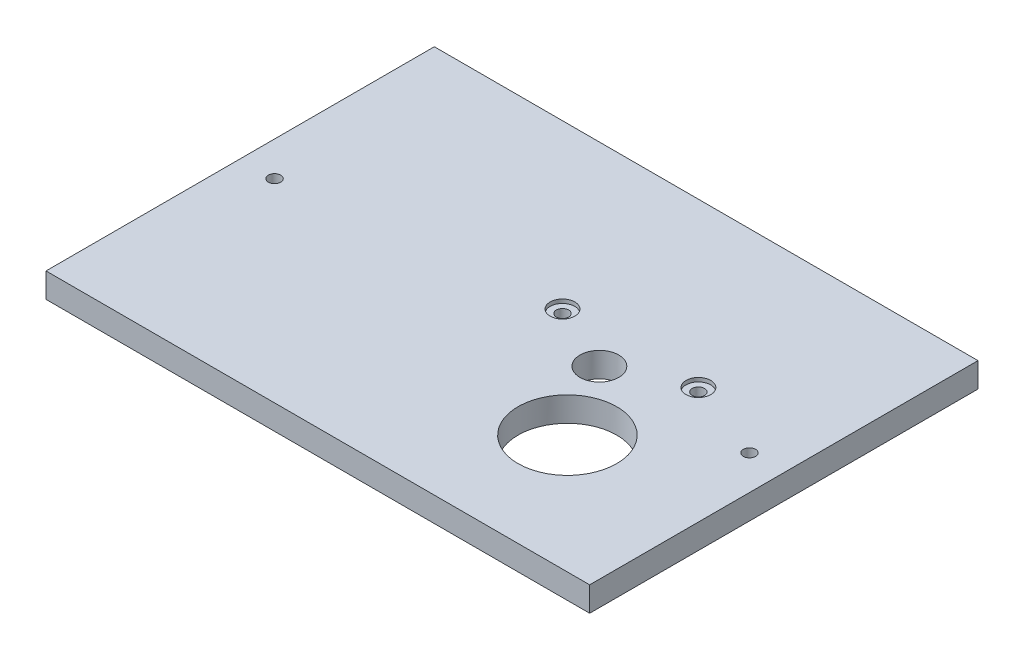
SolidWorks part; units mm, degrees
material "Oak"
ref_plane "Front Plane" through (0, 0, 0) normal (0, 0, 1) x (1, 0, 0)
ref_plane "Top Plane" through (0, 0, 0) normal (0, 1, 0) x (1, 0, 0)
ref_plane "Right Plane" through (0, 0, 0) normal (1, 0, 0) x (0, 0, -1)
sketch "Sketch1" plane through (0, 0, 0) normal (0, 1, 0) x (1, 0, 0)
  line L1 (0, 0) -> (140, 0)
  line L2 (0, 0) -> (0, 100)
  line L3 (0, 100) -> (140, 100)
  line L4 (140, 0) -> (140, 100)
  dimension "D1" = 140
  dimension "D2" = 100
extrude "Boss-Extrude1" add sketch "Sketch1" along normal blind 6.35
sketch "Sketch2" plane through (0, 6.35, 0) normal (0, 1, 0) x (1, 0, 0)
  line L0 (0, 50) -> (140, 50) construction
  line L1 (0, 100) -> (0, 0) construction
  line L2 (140, 0) -> (140, 100) construction
  line L3 (70, 100) -> (70, 0) construction
  line L4 (140, 100) -> (0, 100) construction
  line L5 (0, 0) -> (140, 0) construction
  line L6 (92.5, 50) -> (114.578, 11.7597) construction
  circle A0 centre (103.75, 30.5144) radius 12.705
  circle A1 centre (92.5, 50) radius 5
  point P12 (92.5, 50)
  point P13 (70, 50)
  dimension "D3" = 25.41
  dimension "D5" = 10
  dimension "D1" = 22.5
  dimension "D2" = 120
  dimension "D4" = 22.5
  dimension "D6" = 30.5144
  dimension "D7" = 36.25
extrude "Cut-Extrude1" cut sketch "Sketch2" against normal blind 10
sketch "Sketch3" plane through (0, 6.35, 0) normal (0, 1, 0) x (1, 0, 0)
  line L0 (0, 100) -> (0, 0) construction
  line L1 (140, 0) -> (140, 100) construction
  line L2 (140, 100) -> (0, 100) construction
  circle A0 centre (8.85, 50) radius 1.5875
  circle A1 centre (131.15, 50) radius 1.5875
  circle A2 centre (75, 58) radius 1.5875
  circle A3 centre (110, 58) radius 1.5875
  circle A4 centre (92.5, 50) radius 5 construction
  dimension "D1" = 3.175
  dimension "D2" = 3.175
  dimension "D3" = 3.175
  dimension "D4" = 3.175
  dimension "D9" = 17.5
  dimension "D10" = 8
  dimension "D11" = 17.5
  dimension "D12" = 8
  dimension "D5" = 8.85
  dimension "D6" = 8.85
  dimension "D7" = 50
  dimension "D8" = 50
extrude "Cut-Extrude2" cut sketch "Sketch3" against normal blind 10
sketch "Sketch4" plane through (0, 6.35, 0) normal (0, 1, 0) x (1, 0, 0)
  circle A0 centre (75, 58) radius 1.5875
  circle A1 centre (110, 58) radius 1.5875
  circle A2 centre (110, 58) radius 3.175
  circle A3 centre (75, 58) radius 3.175
  dimension "D1" = 6.35
  dimension "D2" = 6.35
extrude "Cut-Extrude3" cut sketch "Sketch4" against normal blind 1
